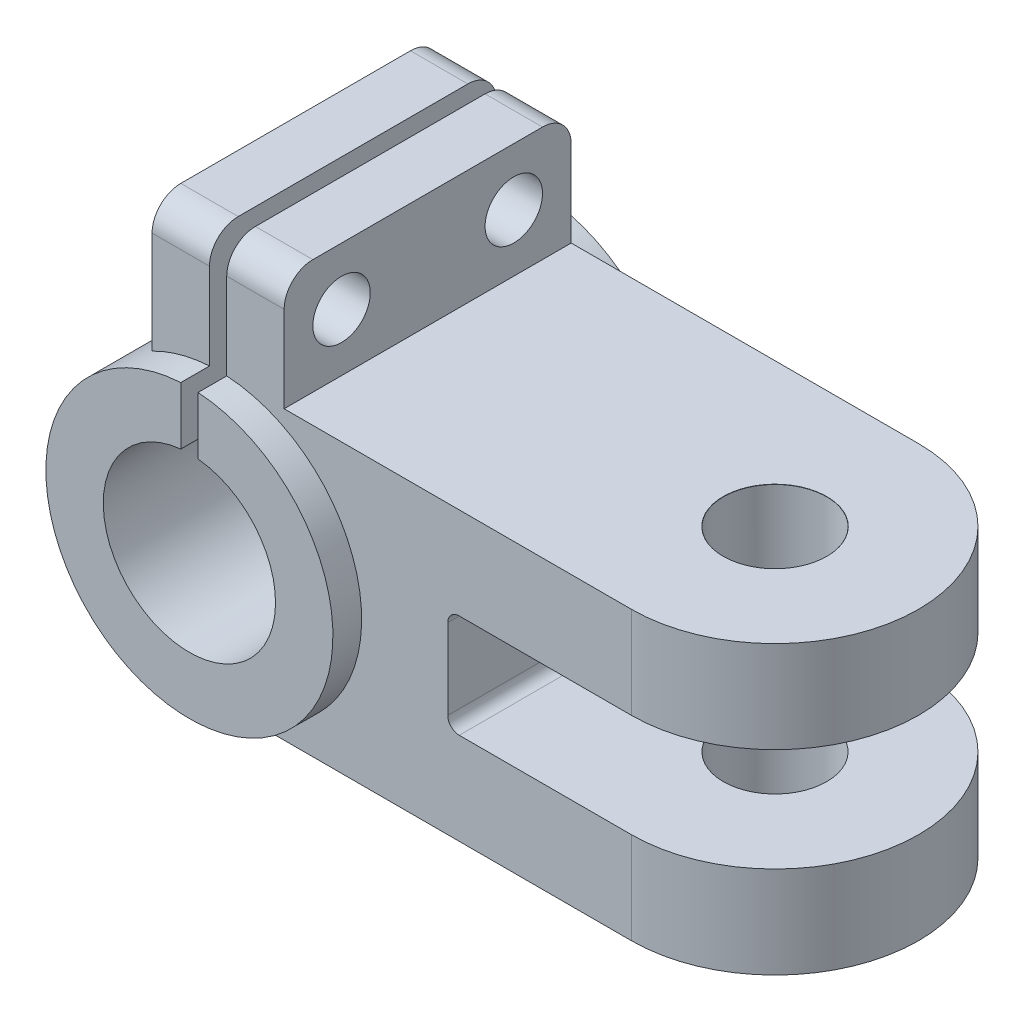
SolidWorks part; units mm, degrees
ref_plane "Piano frontale" through (0, 0, 0) normal (0, 0, 1) x (1, 0, 0)
ref_plane "Piano superiore" through (0, 0, 0) normal (0, 1, 0) x (1, 0, 0)
ref_plane "Piano destro" through (0, 0, 0) normal (1, 0, 0) x (0, 0, -1)
sketch "Schizzo1" plane through (0, 0, 0) normal (0, 0, 1) x (1, 0, 0)
  line L0 (0, 0) -> (0, 50.9441) construction
  line L1 (-43.9945, 0) -> (132.8998, 0) construction
  line L2 (72, 49.2482) -> (72, -40.6316) construction
  line L5 (-11.5, 45) -> (11.5, 45)
  line L7 (-11.5, 45) -> (-11.5, 22.198)
  line L8 (-15.008, 35) -> (15.3925, 35) construction
  line L9 (11.5, 45) -> (11.5, 25)
  line L10 (0, -25) -> (97, -25)
  line L12 (97, -25) -> (97, -9)
  line L13 (97, -9) -> (42, -9)
  line L14 (40, -7) -> (40, 7)
  line L15 (97, 25) -> (11.5, 25)
  line L16 (97, 25) -> (97, 9)
  line L17 (97, 9) -> (42, 9)
  line L31 (0, 0) -> (0, -38.2072) construction
  circle A0 centre (0, 0) radius 25
  circle A1 centre (0, 0) radius 15
  arc A2 (42, -9) -> (40, -7) centre (42, -7) cw
  arc A3 (42, 9) -> (40, 7) centre (42, 7) ccw
  point P35 (40, 0)
  dimension "D2" = 72
  dimension "D3" = 25
  dimension "D5" = 2
  dimension "D11" = 15
  dimension "D12" = 40
  dimension "D4" = 23
  dimension "D6" = 57
  dimension "D7" = 18
  dimension "D8" = 10
  dimension "D9" = 20
  dimension "D10" = 11.5
extrude "Estrusione-Estrusione1" add sketch "Schizzo1" along normal mid plane 60 contours A0 A1 region at (12.623, 20.7559, 0)
extrude "Estrusione-Estrusione2" add sketch "Schizzo1<6>" along normal mid plane 50 contours A3 L17 L16 L15 L9 L5 L7 A0 L10 L12 L13 A2 L14 region at (0, 43.7088, 0)
sketch "Schizzo1<6>" plane through (0, 0, 0) normal (0, 0, 1) x (1, 0, 0) same geometry as "Schizzo1"
sketch "Schizzo3" plane through (0, 0, 30) normal (0, 0, 1) x (1, 0, 0)
  line L0 (0, 0) -> (0, 55.4228) construction
  line L1 (1.5, 45) -> (-1.5, 45)
  line L2 (-11.5, 45) -> (11.5, 45) construction
  line L3 (-1.5, 45) -> (-1.5, 14.9248)
  line L4 (-1.5, 14.9248) -> (0, 15)
  line L5 (1.5, 14.9248) -> (0, 15)
  line L6 (1.5, 45) -> (1.5, 14.9248)
  circle A0 centre (0, 0) radius 15 construction
  point P13 (0, 45)
  dimension "D1" = 3
  dimension "D2" = 1.5
extrude "Taglio-Estrusione1" cut sketch "Schizzo3" against normal through all
hole_wizard "Foro Ø18.0 (18)-1" positions "Schizzo3D2" profile "Schizzo4" hole size "Ø18.0" standard "ISO" end condition through all
sketch3d "Schizzo3D2"
  point P25 (72, 25, 0)
sketch "Schizzo4" plane through (72, 25, 0) normal (1, 0, 0) x (0, 0, 1)
  line L0 (0, 0) -> (0, 50)
  line L1 (0, 50) -> (9, 50)
  line L2 (9, 50) -> (9, 0.025)
  line L3 (9, 0.025) -> (9.025, 0)
  line L5 (9.025, 0) -> (0, 0)
  line L6 (-9, 0.025) -> (-9.025, 0) construction
  line L11 (0, -6.35) -> (0, 107.95) construction
  dimension "Thru Hole Dia." = 18
  dimension "Thru Hole Depth" = 50
  dimension "Near C'Sink Dia." = 18.05
  dimension "Near C'Sink Angle" = 90
hole_wizard "Foro Ø10.0 (10)-1" positions "Schizzo3D6" profile "Schizzo8" hole size "Ø10.0" standard "ISO" end condition through all
sketch3d "Schizzo3D6"
  line L0 (-11.5, 45, 0) -> (-11.5, 22.198, 0) construction
  line L1 (-11.5, 45, 25) -> (-11.5, 45, -25) construction
  line L2 (-11.5, 22.198, 25) -> (-11.5, 22.198, -25) construction
  line L3 (-11.5, 45, -15) -> (-11.5, 29.2799, -15) construction
  line L5 (-11.5, 35, -19.2311) -> (-11.5, 35, -7.8096) construction
  line L7 (-11.5, 45, 15) -> (-11.5, 31.5252, 15) construction
  line L9 (-11.5, 35, 5.1738) -> (-11.5, 35, 17.3763) construction
  point P15 (-11.5, 35, -15)
  point P17 (-11.5, 35, 15)
  point P19 (-11.5, 35, -15)
  point P23 (-11.5, 35, 15)
  dimension "D1" = 30
  dimension "D2" = 10
  dimension "D3" = 10
  dimension "D4" = 15
sketch "Schizzo8" plane through (-11.5, 35, 15) normal (0, 1, 0) x (0, 0, 1)
  line L0 (0, 0) -> (0, 108.5)
  line L1 (0, 108.5) -> (5, 108.5)
  line L2 (5, 108.5) -> (5, 0.025)
  line L3 (5, 0.025) -> (5.025, 0)
  line L5 (5.025, 0) -> (0, 0)
  line L6 (-5, 0.025) -> (-5.025, 0) construction
  line L11 (0, -6.35) -> (0, 107.95) construction
  dimension "Thru Hole Dia." = 10
  dimension "Thru Hole Depth" = 108.5
  dimension "Near C'Sink Dia." = 10.05
  dimension "Near C'Sink Angle" = 90
sketch "Schizzo9" plane through (0, 25, 0) normal (0, 1, 0) x (1, 0, 0)
  line L1 (54.9765, 0) -> (72, 0) construction
  line L2 (72, 0) -> (72, -25) construction
  line L3 (97, -25) -> (11.5, -25) construction
  line L4 (72, -25) -> (72, 25) construction
  line L5 (97, 25) -> (11.5, 25) construction
  line L6 (72, 25) -> (72, 0) construction
  line L7 (72, 0) -> (97, 0) construction
  line L8 (97, -25) -> (97, 25) construction
  line L9 (25, 30) -> (-25, 30) construction
  arc A0 (72, 25) -> (72, -25) centre (72, 0) cw
  dimension "D2" = 25
  dimension "D1" = 30
extrude "Taglio-Estrusione2" cut sketch "Schizzo9" against normal through all and the other way through all
fillet "Raccordo1" radius 5 4 edges at (-6.5, 45, -25) (-6.5, 45, 25) (6.5, 45, 25) (6.5, 45, -25)
